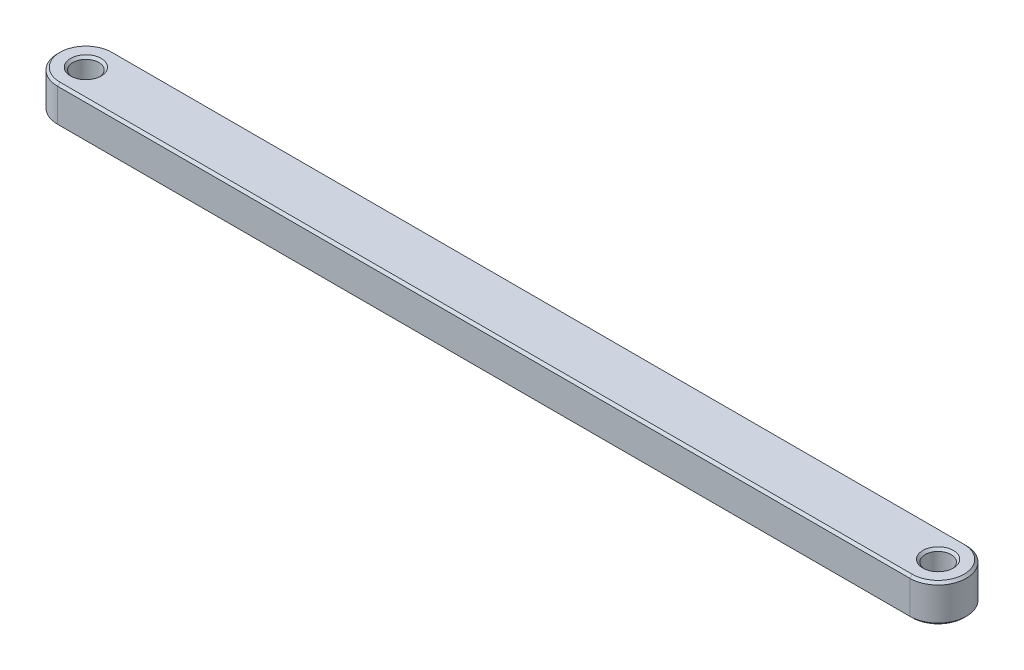
SolidWorks part; units mm, degrees
ref_plane "Front Plane" through (0, 0, 0) normal (0, 0, 1) x (1, 0, 0)
ref_plane "Top Plane" through (0, 0, 0) normal (0, 1, 0) x (1, 0, 0)
ref_plane "Right Plane" through (0, 0, 0) normal (1, 0, 0) x (0, 0, -1)
sketch "Sketch1" plane through (0, 0, 0) normal (0, 1, 0) x (1, 0, 0)
  line L0 (0, 0) -> (143.6841, 0) construction
  line L1 (0, 4.7625) -> (143.6841, 4.7625)
  line L2 (0, -4.7625) -> (143.6841, -4.7625)
  arc A0 (0, 4.7625) -> (0, -4.7625) centre (0, 0) ccw
  arc A1 (143.6841, -4.7625) -> (143.6841, 4.7625) centre (143.6841, 0) ccw
  circle A2 centre (0, 0) radius 2.1828
  circle A3 centre (143.6841, 0) radius 2.1828
  point P3 (71.842, 0)
  dimension "D2" = 4.7625
  dimension "D3" = 4.3656
  dimension "D4" = 4.3656
  dimension "D1" = 143.6841
extrude "Boss-Extrude1" add sketch "Sketch1" along normal blind 6.35
chamfer "Chamfer1" distance 0.3969 angle 45 12 edges at (143.6841, 0, 2.1828) (0, 0, 2.1828) (71.842, 0, 4.7625) (148.4466, 0, 0) (71.842, 0, -4.7625) (-4.7625, 0, 0) (143.6841, 6.35, 2.1828) (71.842, 6.35, -4.7625) (148.4466, 6.35, 0) (71.842, 6.35, 4.7625) (-4.7625, 6.35, 0) (0, 6.35, 2.1828)
